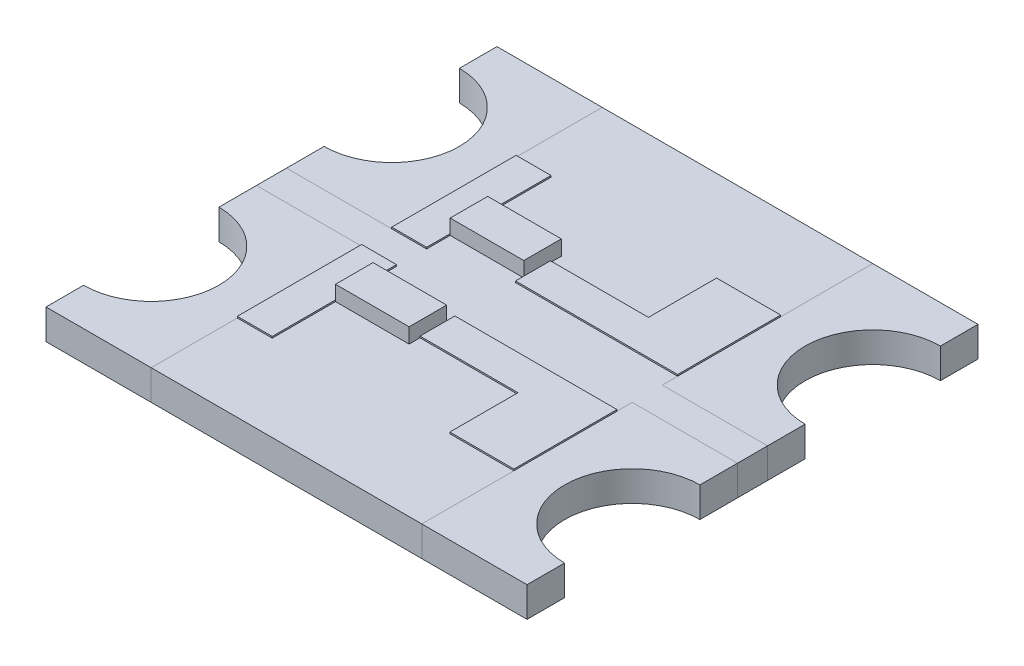
SolidWorks part; units mm, degrees
ref_plane "前视基准面" through (0, 0, 0) normal (0, 0, 1) x (1, 0, 0)
ref_plane "上视基准面" through (0, 0, 0) normal (0, 1, 0) x (1, 0, 0)
ref_plane "右视基准面" through (0, 0, 0) normal (1, 0, 0) x (0, 0, -1)
sketch "草图1" plane through (0, 0, 0) normal (0, 1, 0) x (1, 0, 0)
  line L0 (0, 0.9561) -> (0, -0.9561) construction
  line L1 (-1.1679, 0) -> (1.1679, 0) construction
  line L2 (-0.8, 0.625) -> (-0.8, 0.75)
  line L3 (-0.8, 0.75) -> (0.8, 0.75) construction
  line L4 (-0.8, 0.75) -> (-0.8, -0.75) construction
  line L5 (-0.8, -0.75) -> (0.8, -0.75) construction
  line L6 (0.8, 0.75) -> (0.8, -0.75) construction
  line L7 (-0.8, 0.75) -> (0.8, -0.75) construction
  line L8 (-0.8, -0.75) -> (0.8, 0.75) construction
  line L9 (-0.8, 0.175) -> (-0.8, 0.05)
  line L16 (-0.45, 0.4) -> (-0.45, 0.75)
  line L17 (-0.45, 0.75) -> (-0.8, 0.75)
  line L18 (-0.8, 0.05) -> (-0.45, 0.05)
  line L19 (-0.45, 0.05) -> (-0.45, 0.4)
  line L20 (0.45, 0.05) -> (0.45, 0.4)
  line L21 (0.8, 0.05) -> (0.45, 0.05)
  line L22 (0.45, 0.75) -> (0.8, 0.75)
  line L23 (0.45, 0.4) -> (0.45, 0.75)
  line L24 (0.8, 0.175) -> (0.8, 0.05)
  line L25 (0.8, 0.625) -> (0.8, 0.75)
  line L26 (0.8, -0.175) -> (0.8, -0.05)
  line L27 (0.8, -0.05) -> (0.45, -0.05)
  line L28 (0.45, -0.05) -> (0.45, -0.4)
  line L29 (0.45, -0.4) -> (0.45, -0.75)
  line L30 (0.45, -0.75) -> (0.8, -0.75)
  line L31 (0.8, -0.625) -> (0.8, -0.75)
  line L32 (-0.45, -0.05) -> (-0.45, -0.4)
  line L33 (-0.8, -0.05) -> (-0.45, -0.05)
  line L34 (-0.45, -0.75) -> (-0.8, -0.75)
  line L35 (-0.45, -0.4) -> (-0.45, -0.75)
  line L36 (-0.8, -0.175) -> (-0.8, -0.05)
  line L37 (-0.8, -0.625) -> (-0.8, -0.75)
  arc A0 (-0.8, 0.175) -> (-0.8, 0.625) centre (-0.8, 0.4) ccw
  arc A1 (-0.8, 0.05) -> (-0.8, 0.75) centre (-0.8, 0.4) ccw construction
  arc A2 (0.8, 0.175) -> (0.8, 0.625) centre (0.8, 0.4) cw
  arc A3 (0.8, -0.175) -> (0.8, -0.625) centre (0.8, -0.4) ccw
  arc A4 (-0.8, -0.175) -> (-0.8, -0.625) centre (-0.8, -0.4) cw
  point P0 (0, 0)
  point P4 (0, 0)
  point P8 (0, 0)
  dimension "D3" = 0.45
  dimension "D1" = 1.5
  dimension "D2" = 1.6
  dimension "D4" = 0.4
extrude "凸台-拉伸1" add sketch "草图1" along normal blind 0.1
sketch "草图2" plane through (0, 0, 0) normal (0, 1, 0) x (1, 0, 0)
  line L0 (0, 0.9407) -> (0, -0.9407) construction
  line L1 (-1.3102, 0) -> (1.3102, 0) construction
  line L2 (-0.8, 0.05) -> (-0.8, -0.05)
  line L3 (-0.8, 0.75) -> (0.8, 0.75) construction
  line L4 (-0.8, 0.75) -> (-0.8, -0.75) construction
  line L5 (-0.8, -0.75) -> (0.8, -0.75) construction
  line L6 (0.8, 0.75) -> (0.8, -0.75) construction
  line L7 (-0.8, 0.75) -> (0.8, -0.75) construction
  line L8 (-0.8, -0.75) -> (0.8, 0.75) construction
  line L9 (-0.8, -0.05) -> (-0.45, -0.05)
  line L10 (-0.45, -0.05) -> (-0.45, -0.75)
  line L11 (-0.45, -0.75) -> (0.45, -0.75)
  line L12 (0.45, -0.75) -> (0.45, -0.05)
  line L13 (0.45, -0.05) -> (0.8, -0.05)
  line L14 (0.8, -0.05) -> (0.8, 0.05)
  line L15 (0.8, 0.05) -> (0.45, 0.05)
  line L16 (0.45, 0.05) -> (0.45, 0.75)
  line L17 (0.45, 0.75) -> (-0.45, 0.75)
  line L18 (-0.45, 0.75) -> (-0.45, 0.05)
  line L19 (-0.45, 0.05) -> (-0.8, 0.05)
  point P0 (0, 0)
  point P4 (0, 0)
  point P8 (0, 0)
extrude "凸台-拉伸2" add sketch "草图2" along normal blind 0.1 separate body
sketch "草图3" plane through (0, 0.1, 0) normal (0, 1, 0) x (1, 0, 0)
  line L0 (-1.1888, 0) -> (1.1888, 0) construction
  line L1 (0, 0.8007) -> (0, -0.8007) construction
  line L2 (-0.334, -0.1283) -> (-0.0891, -0.1283)
  line L3 (-0.334, 0.2531) -> (-0.0891, 0.2531)
  line L4 (-0.334, 0.2531) -> (-0.334, 0.1283)
  line L5 (-0.334, 0.1283) -> (-0.0891, 0.1283)
  line L6 (-0.0891, 0.2531) -> (-0.0891, 0.1283)
  line L7 (-0.334, 0.2531) -> (-0.0891, 0.1283) construction
  line L8 (-0.334, 0.1283) -> (-0.0891, 0.2531) construction
  line L9 (-0.0891, -0.2531) -> (-0.0891, -0.1283)
  line L10 (-0.334, -0.2531) -> (-0.0891, -0.2531)
  line L11 (-0.334, -0.2531) -> (-0.334, -0.1283)
  point P0 (-0.2116, 0.1907)
  point P4 (0, 0)
  point P8 (0, 0)
extrude "凸台-拉伸3" add sketch "草图3" along normal blind 0.05 separate body
sketch "草图4" plane through (0, 0.1, 0) normal (0, 1, 0) x (1, 0, 0)
  line L0 (-1.1899, 0) -> (1.1899, 0) construction
  line L1 (0, 0.9053) -> (0, -0.9053) construction
  line L2 (-0.45, 0.4637) -> (-0.3339, 0.4637)
  line L3 (-0.45, 0.75) -> (-0.45, 0.05) construction
  line L4 (-0.3339, 0.4637) -> (-0.334, 0.2531)
  line L5 (-0.334, 0.2531) -> (-0.334, 0.05)
  line L6 (-0.334, 0.05) -> (-0.45, 0.05)
  line L7 (-0.45, 0.05) -> (-0.45, 0.4637)
  line L8 (-0.0891, 0.2169) -> (0.2369, 0.2169)
  line L9 (0.2369, 0.2169) -> (0.2369, 0.4437)
  line L10 (0.2369, 0.4437) -> (0.45, 0.4437)
  line L11 (0.45, 0.75) -> (0.45, 0.05) construction
  line L12 (0.45, 0.4437) -> (0.45, 0.1009)
  line L13 (0.45, 0.1009) -> (-0.0891, 0.1009)
  line L14 (-0.0891, 0.1009) -> (-0.0891, 0.2169)
  line L15 (0.45, -0.1009) -> (-0.0891, -0.1009)
  line L16 (0.45, -0.4437) -> (0.45, -0.1009)
  line L17 (0.2369, -0.4437) -> (0.45, -0.4437)
  line L18 (0.2369, -0.2169) -> (0.2369, -0.4437)
  line L19 (-0.0891, -0.2169) -> (0.2369, -0.2169)
  line L20 (-0.0891, -0.1009) -> (-0.0891, -0.2169)
  line L21 (-0.334, -0.05) -> (-0.45, -0.05)
  line L22 (-0.334, -0.2531) -> (-0.334, -0.05)
  line L23 (-0.3339, -0.4637) -> (-0.334, -0.2531)
  line L24 (-0.45, -0.4637) -> (-0.3339, -0.4637)
  line L25 (-0.45, -0.05) -> (-0.45, -0.4637)
  point P4 (0, 0)
  point P8 (0, 0)
extrude "凸台-拉伸4" add sketch "草图4" along normal blind 0.005 separate body
sketch "草图6" plane through (0, 0, 0) normal (0, -1, 0) x (1, 0, 0)
  line L0 (-1.4921, 0) -> (1.4921, 0) construction
  line L2 (0, 1.0478) -> (0, -1.0478) construction
  line L3 (0.45, -0.75) -> (-0.45, -0.75) construction
  line L4 (0.1948, 0.75) -> (0.4271, 0.75)
  line L5 (0.1948, 0.75) -> (0.1948, 0.1047)
  line L6 (0.1948, -0.75) -> (0.4271, -0.75)
  line L7 (0.4271, 0.75) -> (0.4271, -0.75)
  line L8 (0.1948, 0.75) -> (0.4271, -0.75) construction
  line L9 (0.1948, -0.75) -> (0.4271, 0.75) construction
  line L10 (0.1948, -0.1047) -> (0.1948, -0.75)
  line L11 (-0.1948, 0.1047) -> (0.1948, 0.1047)
  line L12 (-0.1948, 0.1047) -> (-0.1948, -0.1047)
  line L13 (-0.1948, -0.1047) -> (0.1948, -0.1047)
  line L15 (-0.1948, 0.1047) -> (0.1948, -0.1047) construction
  line L16 (-0.1948, -0.1047) -> (0.1948, 0.1047) construction
  point P0 (0.3109, 0)
  point P3 (0, 0)
  point P7 (0, 0)
  point P14 (0, 0)
wrap "包覆1" sketch "草图6" wrap type scribe source sketch "草图6" face at (0, 0, 0)
